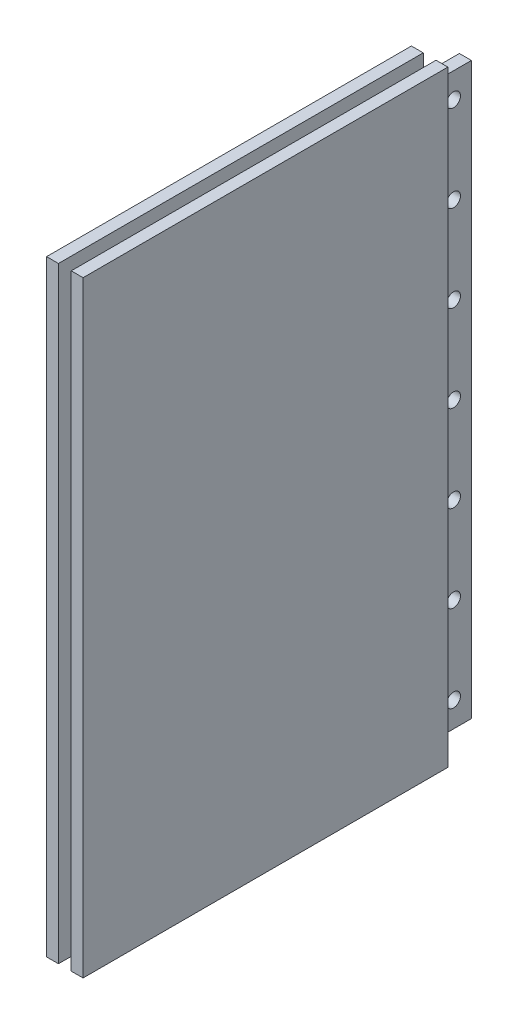
SolidWorks part; units mm, degrees
ref_plane "Front Plane" through (0, 0, 0) normal (1, 0, 0) x (0, 1, 0)
ref_plane "Top Plane" through (0, 0, 0) normal (0, 0, 1) x (0, 1, 0)
ref_plane "Right Plane" through (0, 0, 0) normal (0, 1, 0) x (-1, 0, 0)
sketch "Sketch1" plane through (0, 0, 0) normal (1, 0, 0) x (0, 1, 0)
  line L1 (0, 0) -> (166.25, 0)
  line L2 (0, 0) -> (0, 100)
  line L3 (0, 100) -> (166.25, 100)
  line L4 (166.25, 0) -> (166.25, 100)
  dimension "D1" = 166.25
  dimension "D2" = 100
extrude "Boss-Extrude1" add sketch "Sketch1" against normal blind 10
sketch "Sketch2" plane through (0, 166.25, 0) normal (0, 1, 0) x (-1, 0, 0)
  line L0 (0, 0) -> (3.35, 0) construction
  line L1 (0, 0) -> (0, -9.8) construction
  line L2 (0, -9.8) -> (3.35, -9.8) construction
  line L3 (3.35, 0) -> (3.35, -9.8) construction
  line L4 (10, 0) -> (6.65, 0) construction
  line L5 (10, 0) -> (10, -9.8) construction
  line L6 (10, -9.8) -> (6.65, -9.8) construction
  line L7 (6.65, 0) -> (6.65, -9.8) construction
  line L8 (6.65, -9.8) -> (3.35, -9.8)
  line L9 (6.65, -9.8) -> (6.65, 0)
  line L10 (6.65, 0) -> (3.35, 0)
  line L11 (3.35, -9.8) -> (3.35, 0)
  line L12 (10, 0) -> (10, 100) construction
  line L13 (10, 0) -> (0, 0) construction
  dimension "D1" = 3.35
  dimension "D2" = 3.35
  dimension "D3" = 9.8
extrude "Boss-Extrude2" add sketch "Sketch2" against normal up to surface (166.25 mm away) up to face at (-5, 0, 50)
ref_plane "Plane1" through (0, 83.125, 0) normal (0, 1, 0) x (1, 0, 0)
sketch "Sketch3" plane through (0, 166.25, 0) normal (0, 1, 0) x (-1, 0, 0)
  line L0 (0, 100) -> (3.25, 100) construction
  line L1 (0, 100) -> (0, -9.8) construction
  line L2 (0, -9.8) -> (3.25, -9.8) construction
  line L3 (3.25, 100) -> (3.25, -9.8) construction
  line L4 (6.75, -9.8) -> (10, -9.8) construction
  line L5 (6.75, -9.8) -> (6.75, 100) construction
  line L6 (6.75, 100) -> (10, 100) construction
  line L7 (10, -9.8) -> (10, 100) construction
  line L8 (3.25, 100) -> (6.75, 100)
  line L9 (3.25, 100) -> (3.25, -9.8)
  line L10 (3.25, -9.8) -> (6.75, -9.8)
  line L11 (6.75, 100) -> (6.75, -9.8)
  line L12 (10, 100) -> (0, 100) construction
  line L13 (0, 0) -> (0, 100) construction
  line L15 (3.35, -9.8) -> (6.65, -9.8) construction
  dimension "D1" = 3.25
  dimension "D2" = 3.25
extrude "Cut-Extrude1" cut sketch "Sketch3" against normal blind 5
mirror "Mirror1" about plane through (0, 83.125, 0) normal (0, 1, 0) of "Cut-Extrude1"
sketch "Sketch4" plane through (-3.35, 0, 0) normal (1, 0, 0) x (0, 1, 0)
  line L0 (5, -9.8) -> (161.25, -9.8) construction
  line L1 (0, 0) -> (11.875, 0) construction
  line L2 (0, 0) -> (0, -9.8) construction
  line L3 (0, -9.8) -> (11.875, -9.8) construction
  line L4 (11.875, 0) -> (11.875, -9.8) construction
  circle A0 centre (11.875, -4.9) radius 1.9
  dimension "D2" = 3.8
  dimension "D1" = 11.875
extrude "Cut-Extrude2" cut sketch "Sketch4" against normal up to next
pattern_linear "LPattern1" count 7 spacing 23.75 along (0, 1, 0) of "Cut-Extrude2"
sketch "Sketch5" plane through (0, 0, 100) normal (0, 0, 1) x (1, 0, 0)
  line L1 (-6.75, 161.25) -> (-3.25, 161.25)
  line L2 (-6.75, 161.25) -> (-6.75, 5)
  line L3 (-6.75, 5) -> (-3.25, 5)
  line L4 (-3.25, 161.25) -> (-3.25, 5)
  dimension "D1" = 3.5
extrude "Cut-Extrude3" cut sketch "Sketch5" against normal blind 5
sketch "Sketch6" plane through (-10, 0, 0) normal (1, 0, 0) x (0, 1, 0)
  line L0 (166.25, 100) -> (0, 100) construction
  line L1 (5, 0) -> (161.25, 0) construction
  line L2 (5, 0) -> (5, 100) construction
  line L3 (5, 100) -> (161.25, 100) construction
  line L4 (161.25, 0) -> (161.25, 100) construction
  line L5 (10, 90) -> (10, 5)
  line L6 (5, 100) -> (161.25, 100) construction
  line L7 (5, 100) -> (5, 95) construction
  line L8 (5, 95) -> (161.25, 95) construction
  line L9 (161.25, 100) -> (161.25, 95) construction
  line L10 (5, 95) -> (161.25, 95)
  line L11 (5, 95) -> (5, 0)
  line L12 (5, 0) -> (161.25, 0)
  line L13 (161.25, 95) -> (161.25, 0)
  line L14 (10, 5) -> (156.25, 5)
  line L15 (156.25, 90) -> (156.25, 5)
  line L16 (10, 90) -> (156.25, 90)
  dimension "D1" = 5
  dimension "D2" = 5
extrude "Cut-Extrude4" cut sketch "Sketch6" along normal blind 5 contours L5 L16 L15 L14
chamfer "Chamfer1" distance 2.5 distance2 5 4 edges at (-10, 10, 47.5) (-10, 83.125, 5) (-10, 156.25, 47.5) (-10, 83.125, 90)
equation "\"whitekey_cutout_length\"= 101.5"
equation "\"whitekey_spacing\"=1.25"
equation "\"key_mount_recess_length\"=50"
equation "\"key_mount_recess_height\"=12.5"
equation "\"key_mount_recess_depth\"=1.5"
equation "\"wall_thickness\"=10"
equation "\"guide_brace_height\"=20"
equation "\"guide_brace_thickness\"=2"
equation "\"dowel_recess_depth\"=10"
equation "\"dowel_recess_offset\"=3.25"
equation "\"dowel_insert_tolerance\"=0.1"
equation "\"base_mount_height\"=40"
equation "\"base_rear_length\"=80"
equation "\"base_front_length\"=111.5"
equation "\"screw_hole_wall_offset\"=7.25"
equation "\"screw_hole_edge_inset\"=\"dowel_recess_depth\"/2"
equation "\"screw_hole_diameter\"=3.8"
equation "\"screw_head_hole_diameter\"=6.7"
equation "\"screw_nut_hole_side_len\"=3.5"
equation "\"screw_nut_recess_offset\"=0.35"
equation "\"screw_head_and_nut_recess_depth\"=2.5"
equation "\"screw_shaft_diameter\"=3.5"
equation "\"switch_board_width\"=30"
equation "\"switch_board_thickness\"=1.6"
equation "\"switch_board_wall_offset\"=11.5"
equation "\"heatset_insert_hole_diameter\"=4.8"
equation "\"heatset_insert_hole_depth\"=3.8"
equation "\"front_rear_panel_width\"=23.75"
equation "\"front_panel_height\"=24"
equation "\"front_rear_panel_recess_depth\"=5"
equation "\"rod_diameter\"=5"
equation "\"rod_head_diameter\"=8"
equation "\"rod_length_adj\"=0.5"
equation "\"rod_insert_length\"=2.8"
equation "\"switch_black_key_mount_height\"=8"
equation "\"switch_white_key_mount_height\"=3"
equation "\"side_panel_depth\"=35"
equation "\"interface_panel_height\"=135"
equation "\"interface_panel_roof_length\"=50"
equation "\"D2@Sketch1\"=\"base_mount_height\"+\"wall_thickness\"+\"rear_center_panel_height_adjust\""
equation "\"D1@Sketch1\"=\"front_rear_panel_width\"*7"
equation "\"D1@Boss-Extrude1\"=\"wall_thickness\""
equation "\"D1@Sketch2\"=\"dowel_recess_offset\"+\"dowel_insert_tolerance\""
equation "\"D2@Sketch2\"=\"dowel_recess_offset\"+\"dowel_insert_tolerance\""
equation "\"D3@Sketch2\"=\"dowel_recess_depth\"-\"dowel_insert_tolerance\"*2"
equation "\"D1@Sketch3\"=\"dowel_recess_offset\""
equation "\"D2@Sketch3\"=\"dowel_recess_offset\""
equation "\"D1@Cut-Extrude1\"=\"front_rear_panel_recess_depth\""
equation "\"D1@Sketch4\"=\"front_rear_panel_width\"/2"
equation "\"D2@Sketch4\"=\"screw_hole_diameter\""
equation "\"D3@LPattern1\"=\"front_rear_panel_width\""
equation "\"D1@Cut-Extrude3\"=\"front_rear_panel_recess_depth\""
equation "\"D1@Sketch6\"=\"front_rear_panel_recess_depth\""
equation "\"D1@Cut-Extrude4\"=\"wall_thickness\"/2"
equation "\"rear_center_panel_height_adjust\"=50"
